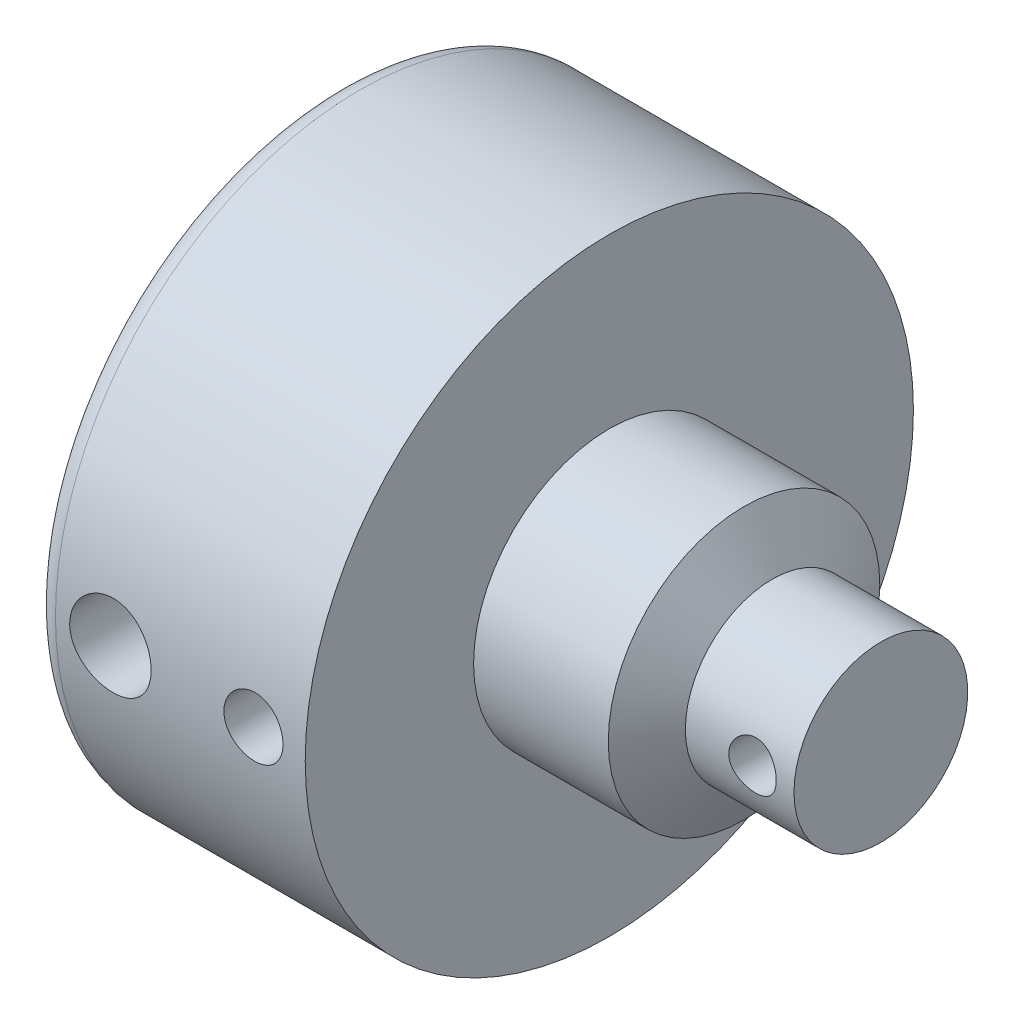
SolidWorks part; units mm, degrees
material "1060 Alloy"
ref_plane "Front Plane" through (0, 0, 0) normal (0, 0, 1) x (1, 0, 0)
ref_plane "Top Plane" through (0, 0, 0) normal (0, 1, 0) x (1, 0, 0)
ref_plane "Right Plane" through (0, 0, 0) normal (1, 0, 0) x (0, 0, -1)
ref_axis "X-axis" through (-88.99, 0, 0) along (1, 0, 0)
ref_axis "Y-axis" through (0, 55, 0) along (0, -1, 0)
ref_axis "Z-axis" through (0, 0, -88.99) along (0, 0, 1)
sketch "Sketch1" plane through (0, 0, 0) normal (0, 0, 1) x (1, 0, 0)
  line L0 (-11.048, 0) -> (11.3061, 0) construction
  line L1 (0, 0) -> (0, -10.6608) construction
  line L2 (0, 0) -> (0, 17.78)
  line L3 (0, 17.78) -> (15.875, 17.78)
  line L4 (15.875, 17.78) -> (15.875, 7.9375)
  line L12 (9.9638, 0) -> (0, 0)
  line L13 (15.875, 7.9375) -> (23.7502, 7.9375)
  line L14 (23.7502, 7.9375) -> (25.4, 5.08)
  line L15 (25.4, 5.08) -> (31.75, 5.08)
  line L16 (31.75, 5.08) -> (31.75, 0)
  line L17 (31.75, 0) -> (9.9638, 0)
  line L18 (25.4, 5.08) -> (25.4, 11.0422) construction
  dimension "D1" = 15.875
  dimension "D2" = 9.525
  dimension "D3" = 31.75
  dimension "D4" = 35.56
  dimension "D5" = 15.875
  dimension "D6" = 10.16
  dimension "D7" = 30
revolve "Revolve1" add sketch "Sketch1" angle 360 about axis through (-88.99, 0, 0) along (1, 0, 0)
hole_wizard "#29 (0.136) Diameter Hole1" positions "3DSketch2" profile "Sketch3" hole size "#29" standard "ANSI Inch" end condition through all
sketch3d "3DSketch2"
  point P0 (12.8465, 0.1707, 17.7792)
sketch "Sketch3" plane through (12.8465, 0.1707, 17.7792) normal (1, 0, 0) x (0, -1, 0.0096)
  line L0 (0, 0) -> (0, 35.7299)
  line L1 (0, 35.7299) -> (1.7272, 35.7299)
  line L2 (1.7272, 35.7299) -> (1.7272, 0)
  line L5 (1.7272, 0) -> (0, 0)
  line L11 (0, -6.35) -> (0, 107.95) construction
  dimension "Thru Hole Dia." = 3.4544
  dimension "Thru Hole Depth" = 35.7299
hole_wizard "7/64 (0.10938) Diameter Hole1" positions "3DSketch3" profile "Sketch4" hole size "7/64" standard "ANSI Inch" end condition through all
sketch3d "3DSketch3"
  line L0 (0, 0, 0) -> (41.2628, 0, 0) construction
  point P0 (29.3243, 0.0624, 5.0796)
sketch "Sketch4" plane through (29.3243, 0.0624, 5.0796) normal (1, 0, 0) x (0, -0.9999, 0.0123)
  line L0 (0, 0) -> (0, 23.0771)
  line L1 (0, 23.0771) -> (1.3891, 23.0771)
  line L2 (1.3891, 23.0771) -> (1.3891, 0)
  line L5 (1.3891, 0) -> (0, 0)
  line L11 (0, -6.35) -> (0, 107.95) construction
  dimension "Thru Hole Dia." = 2.7783
  dimension "Thru Hole Depth" = 23.0771
hole_wizard "3/16 (0.1875) Diameter Hole1" positions "3DSketch4" profile "Sketch5" hole size "3/16" standard "ANSI Inch" end condition through all
sketch3d "3DSketch4"
  point P0 (4.4838, 0.0764, 17.7798)
sketch "Sketch5" plane through (4.4838, 0.0764, 17.7798) normal (1, 0, 0) x (0, -1, 0.0043)
  line L0 (0, 0) -> (0, 35.6363)
  line L1 (0, 35.6363) -> (2.3812, 35.6363)
  line L2 (2.3812, 35.6363) -> (2.3812, 0)
  line L5 (2.3812, 0) -> (0, 0)
  line L11 (0, -6.35) -> (0, 107.95) construction
  dimension "Thru Hole Dia." = 4.7625
  dimension "Thru Hole Depth" = 35.6363
fillet "Fillet1" radius 1.27 1 edges at (0, 0, 17.78)
